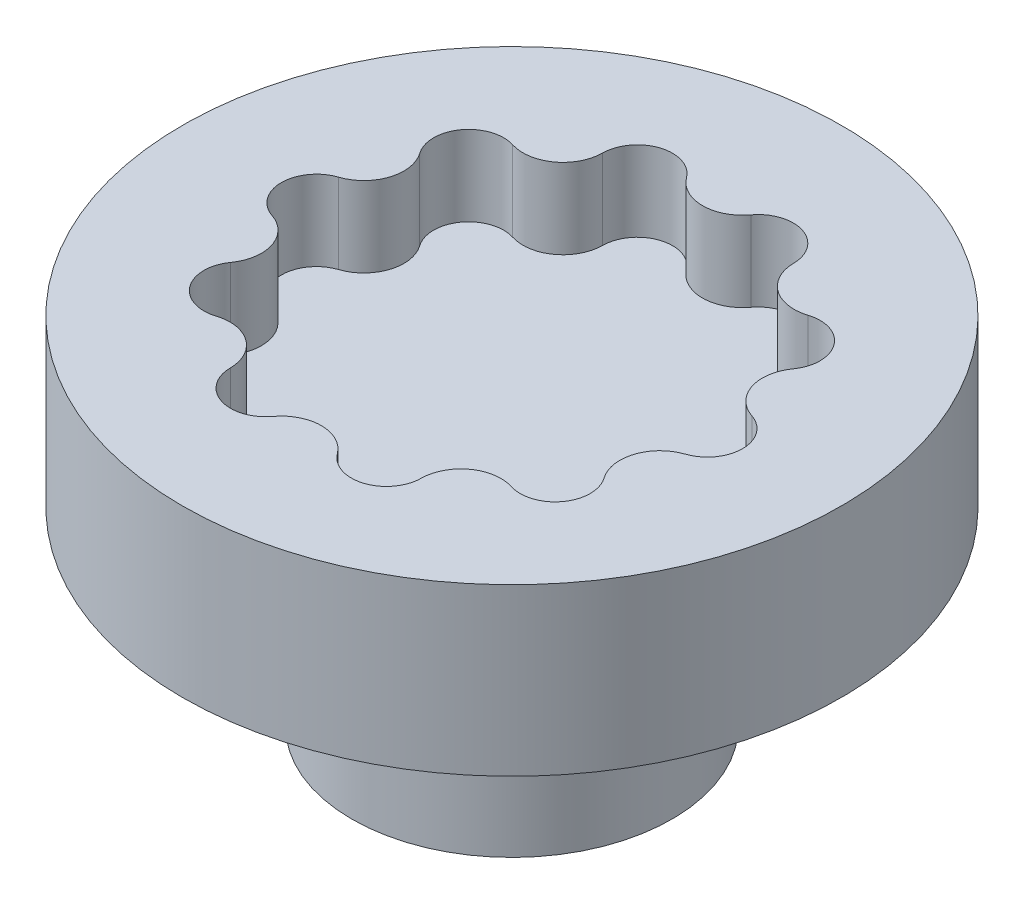
SolidWorks part; units mm, degrees
ref_plane "Front" through (0, 0, 0) normal (0, 0, 1) x (1, 0, 0)
ref_plane "Top" through (0, 0, 0) normal (0, 1, 0) x (1, 0, 0)
ref_plane "Right" through (0, 0, 0) normal (1, 0, 0) x (0, 0, -1)
sketch "Sketch1" plane through (0, 0, 0) normal (0, 1, 0) x (1, 0, 0)
  circle A0 centre (0, 0) radius 26.1937 construction
  circle A1 centre (0, 0) radius 26.143
  dimension "D1" = 52.3875
  dimension "D2" = 0.0508
extrude "Boss-Extrude1" add sketch "Sketch1" against normal blind 6.8104
sketch "Sketch2" plane through (0, -6.8104, 0) normal (0, -1, 0) x (1, 0, 0)
  circle A0 centre (0, 0) radius 12.7
  dimension "D1" = 25.4
extrude "Boss-Extrude2" add sketch "Sketch2" along normal blind 15.0812
sketch "Sketch3" plane through (0, 0, 0) normal (0, 1, 0) x (1, 0, 0)
  line L0 (0, 0) -> (0, 26.143) construction
  line L1 (0, 0) -> (15.3664, 21.1501) construction
  arc A0 (2.553, 16.4005) -> (7.5745, 14.7689) centre (4.7912, 14.7457) cw
  circle A2 centre (0, 0) radius 18.288 construction
  arc A3 (0, 15.113) -> (2.553, 16.4005) centre (0, 18.288) ccw
  arc A4 (8.8832, 12.2267) -> (7.5745, 14.7689) centre (10.7494, 14.7953) cw
  arc A5 (8.8832, 12.2267) -> (11.7054, 11.7676) centre (10.7494, 14.7953) ccw
  arc A6 (11.7054, 11.7676) -> (14.8088, 7.4961) centre (12.5434, 9.1133) cw
  arc A7 (14.3733, 4.6702) -> (14.8088, 7.4961) centre (17.3929, 5.6513) cw
  arc A8 (14.3733, 4.6702) -> (16.3867, 2.64) centre (17.3929, 5.6513) ccw
  arc A9 (16.3867, 2.64) -> (16.3867, -2.64) centre (15.5045, 0) cw
  arc A10 (14.3733, -4.6702) -> (16.3867, -2.64) centre (17.3929, -5.6513) cw
  arc A11 (14.3733, -4.6702) -> (14.8088, -7.4961) centre (17.3929, -5.6513) ccw
  arc A12 (14.8088, -7.4961) -> (11.7054, -11.7676) centre (12.5434, -9.1133) cw
  arc A13 (8.8832, -12.2267) -> (11.7054, -11.7676) centre (10.7494, -14.7953) cw
  arc A14 (8.8832, -12.2267) -> (7.5745, -14.7689) centre (10.7494, -14.7953) ccw
  arc A15 (7.5745, -14.7689) -> (2.553, -16.4005) centre (4.7912, -14.7457) cw
  arc A16 (0, -15.113) -> (2.553, -16.4005) centre (0, -18.288) cw
  arc A17 (0, -15.113) -> (-2.553, -16.4005) centre (0, -18.288) ccw
  arc A18 (-2.553, -16.4005) -> (-7.5745, -14.7689) centre (-4.7912, -14.7457) cw
  arc A19 (-8.8832, -12.2267) -> (-7.5745, -14.7689) centre (-10.7494, -14.7953) cw
  arc A20 (-8.8832, -12.2267) -> (-11.7054, -11.7676) centre (-10.7494, -14.7953) ccw
  arc A21 (-11.7054, -11.7676) -> (-14.8088, -7.4961) centre (-12.5434, -9.1133) cw
  arc A22 (-14.3733, -4.6702) -> (-14.8088, -7.4961) centre (-17.3929, -5.6513) cw
  arc A23 (-14.3733, -4.6702) -> (-16.3867, -2.64) centre (-17.3929, -5.6513) ccw
  arc A24 (-16.3867, -2.64) -> (-16.3867, 2.64) centre (-15.5045, 0) cw
  arc A25 (-14.3733, 4.6702) -> (-16.3867, 2.64) centre (-17.3929, 5.6513) cw
  arc A26 (-14.3733, 4.6702) -> (-14.8088, 7.4961) centre (-17.3929, 5.6513) ccw
  arc A27 (-14.8088, 7.4961) -> (-11.7054, 11.7676) centre (-12.5434, 9.1133) cw
  arc A28 (-8.8832, 12.2267) -> (-11.7054, 11.7676) centre (-10.7494, 14.7953) cw
  arc A29 (-8.8832, 12.2267) -> (-7.5745, 14.7689) centre (-10.7494, 14.7953) ccw
  arc A30 (-7.5745, 14.7689) -> (-2.553, 16.4005) centre (-4.7912, 14.7457) cw
  arc A31 (0, 15.113) -> (-2.553, 16.4005) centre (0, 18.288) cw
  circle A32 centre (0, 0) radius 26.143
  circle A33 centre (0, 0) radius 26.143 construction
  point P78 (0, 0)
  dimension "D1" = 36.576
  dimension "D2" = 3.175
  dimension "D3" = 36
extrude "Boss-Extrude3" add sketch "Sketch3" along normal blind 6.35
hole_wizard "1/4-20 Tapped Hole1" positions "Sketch5" profile "Sketch4" tap size "1/4-20" standard "ANSI Inch"
sketch "Sketch5" plane through (0, -21.8916, 0) normal (0, -1, 0) x (-1, 0, 0)
  circle A1 centre (0, 0) radius 6.35
  circle A3 centre (0, 0) radius 12.7 construction
  point P2 (0, 6.35)
  point P23 (5.4993, -3.175)
  point P24 (-5.4993, -3.175)
  dimension "D2" = 3
sketch "Sketch4" plane through (0, -21.8916, -6.35) normal (1, 0, 0) x (0, 0, -1)
  line L0 (0, 0) -> (0, 18.0438)
  line L1 (0, 18.0438) -> (2.5527, 16.51)
  line L2 (2.5527, 16.51) -> (2.5527, 0)
  line L5 (2.5527, 0) -> (0, 0)
  line L10 (0, 18.0438) -> (-2.5527, 16.51) construction
  line L11 (0, -6.35) -> (0, 107.95) construction
  dimension "Tap Drill Dia." = 5.1054
  dimension "Tap Drill Depth" = 16.51
  dimension "Drill Angle" = 118
